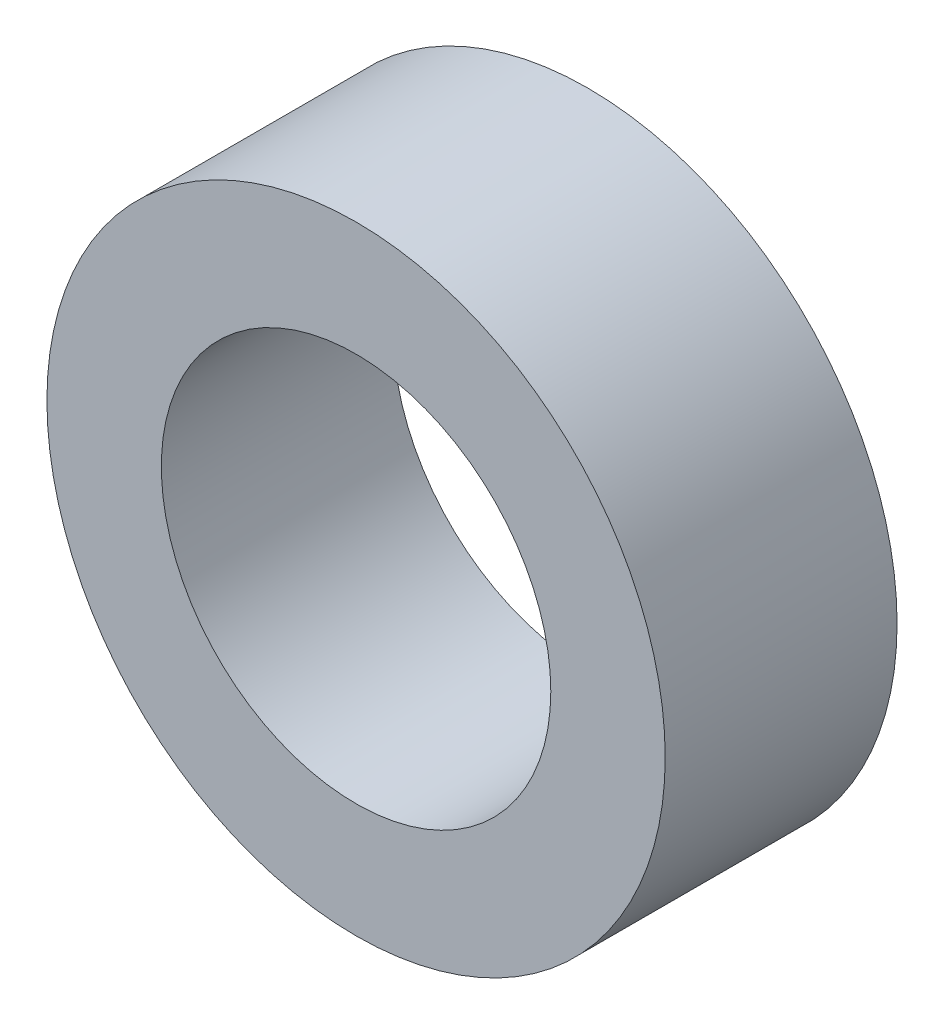
SolidWorks part; units mm, degrees
material "POLYURETHANE (11671)"
ref_plane "Front Plane" through (0, 0, 0) normal (0, 0, 1) x (1, 0, 0)
ref_plane "Top Plane" through (0, 0, 0) normal (0, 1, 0) x (1, 0, 0)
ref_plane "Right Plane" through (0, 0, 0) normal (1, 0, 0) x (0, 0, -1)
sketch "Sketch1" plane through (0, 0, 1577.6299) normal (0, 0, -1) x (-1, 0, 0)
  circle A0 centre (-226.7802, 617.2016) radius 4 construction
  circle A1 centre (-226.7802, 617.2016) radius 4
  circle A2 centre (-226.7802, 617.2016) radius 6.35
extrude "Boss-Extrude1" add sketch "Sketch1" along normal blind 4.7625 contours A2
extrude "Cut-Extrude1" cut sketch "Sketch1<3>" along normal blind 4.7625 contours A1
sketch "Sketch1<3>" plane through (0, 0, 1577.6299) normal (0, 0, -1) x (-1, 0, 0) same geometry as "Sketch1"
